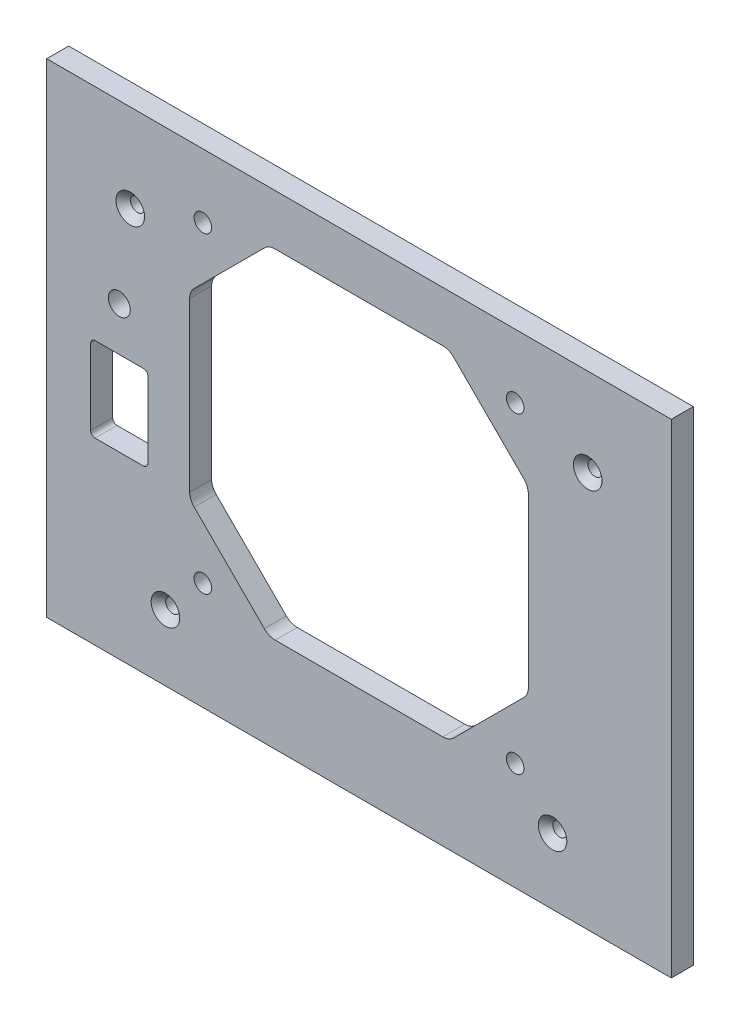
SolidWorks part; units mm, degrees
material "Polycarbonate (PC)"
ref_plane "Front Plane" through (0, 0, 0) normal (0, 0, 1) x (1, 0, 0)
ref_plane "Top Plane" through (0, 0, 0) normal (0, 1, 0) x (1, 0, 0)
ref_plane "Right Plane" through (0, 0, 0) normal (1, 0, 0) x (0, 0, -1)
sketch "Sketch1" plane through (0, 0, 0) normal (0, 0, 1) x (1, 0, 0)
  line L1 (71, -55) -> (-71, -55)
  line L2 (71, -55) -> (71, 55)
  line L3 (71, 55) -> (-71, 55)
  line L4 (-71, -55) -> (-71, 55)
  line L5 (71, -55) -> (-71, 55) construction
  line L6 (71, 55) -> (-71, -55) construction
  point P0 (0, 0)
  dimension "D1" = 142
  dimension "D2" = 110
extrude "Sheet" add sketch "Sketch1" along normal mid plane 5
sketch "Sketch7" plane through (0, 0, 2.5) normal (0, 0, 1) x (1, 0, 0)
  line L0 (-20.5, 43.5) -> (-38.5, 25.5)
  line L1 (20.5, -33.5) -> (-20.5, -33.5)
  line L2 (38.5, -15.5) -> (38.5, 25.5)
  line L3 (20.5, 43.5) -> (-20.5, 43.5)
  line L4 (-38.5, -15.5) -> (-38.5, 25.5)
  line L5 (38.5, -33.5) -> (-38.5, 43.5) construction
  line L6 (38.5, 43.5) -> (-38.5, -33.5) construction
  line L7 (-20.5, -33.5) -> (-38.5, -15.5)
  line L8 (38.5, -15.5) -> (20.5, -33.5)
  line L9 (38.5, 25.5) -> (20.5, 43.5)
  circle A0 centre (0, 5) radius 38.5 construction
  circle A1 centre (-35.5, -30.5) radius 2
  circle A2 centre (35.5, -30.5) radius 2
  circle A3 centre (35.5, 40.5) radius 2
  circle A4 centre (-35.5, 40.5) radius 2
  dimension "D3" = 4
  dimension "D10" = 77
  dimension "D2" = 5
  dimension "D4" = 71
  dimension "D5" = 71
  dimension "D11" = 77
extrude "FanHoles" cut sketch "Sketch7" against normal through all
chamfer "FanChamfer" [suppressed] distance 3 angle 45
fillet "Fillet1" radius 3.5 8 edges at (38.5, 25.5, 0) (38.5, -15.5, 0) (20.5, -33.5, 0) (-38.5, -15.5, 0) (-38.5, 25.5, 0) (-20.5, 43.5, 0) (20.5, 43.5, 0) (-20.5, -33.5, 0)
hole_wizard "Ø3.2 (3.2) TopMountHoles" positions "Sketch9" profile "Sketch10" hole size "Ø3.2" standard "ANSI Metric" end condition through all
sketch "Sketch9" plane through (0, 0, 2.5) normal (0, 0, 1) x (1, 0, 0)
  line L0 (71, 55) -> (-71, 55) construction
  line L1 (-71, 55) -> (-71, -55) construction
  line L2 (71, -55) -> (71, 55) construction
  point P0 (-52, 35)
  point P2 (52, 35)
  dimension "D1" = 20
  dimension "D2" = 19
  dimension "D3" = 19
sketch "Sketch10" plane through (-52, 35, 2.5) normal (1, 0, 0) x (0, -1, 0)
  line L0 (0, 0) -> (0, 5)
  line L1 (0, 5) -> (1.6, 5)
  line L2 (1.6, 5) -> (1.6, 1.65)
  line L3 (1.6, 1.65) -> (3.25, 0)
  line L5 (3.25, 0) -> (0, 0)
  line L6 (-1.6, 1.65) -> (-3.25, 0) construction
  line L11 (0, -6.35) -> (0, 107.95) construction
  dimension "Thru Hole Dia." = 3.2
  dimension "Thru Hole Depth" = 5
  dimension "Near C'Sink Dia." = 6.5
  dimension "Near C'Sink Angle" = 90
hole_wizard "Ø3.2 (3.2) BottomMountHoles" positions "Sketch11" profile "Sketch12" hole size "Ø3.2" standard "ANSI Metric" end condition through all
sketch "Sketch11" plane through (0, 0, 2.5) normal (0, 0, 1) x (1, 0, 0)
  line L0 (-71, -55) -> (71, -55) construction
  line L1 (-71, 55) -> (-71, -55) construction
  line L2 (71, -55) -> (71, 55) construction
  point P0 (-44, -40)
  point P2 (44, -40)
  dimension "D1" = 15
  dimension "D2" = 27
  dimension "D3" = 27
sketch "Sketch12" plane through (-44, -40, 2.5) normal (1, 0, 0) x (0, -1, 0)
  line L0 (0, 0) -> (0, 5)
  line L1 (0, 5) -> (1.6, 5)
  line L2 (1.6, 5) -> (1.6, 1.65)
  line L3 (1.6, 1.65) -> (3.25, 0)
  line L5 (3.25, 0) -> (0, 0)
  line L6 (-1.6, 1.65) -> (-3.25, 0) construction
  line L11 (0, -6.35) -> (0, 107.95) construction
  dimension "Thru Hole Dia." = 3.2
  dimension "Thru Hole Depth" = 5
  dimension "Near C'Sink Dia." = 6.5
  dimension "Near C'Sink Angle" = 90
sketch "Sketch13" plane through (0, 0, 2.5) normal (0, 0, 1) x (1, 0, 0)
  line L0 (-71, 55) -> (-71, -55) construction
  line L1 (-60, 5) -> (-49, 5)
  line L2 (-61, 4) -> (-61, -13.2)
  line L3 (-60, -14.2) -> (-49, -14.2)
  line L4 (-48, 4) -> (-48, -13.2)
  line L5 (71, 55) -> (-71, 55) construction
  arc A0 (-49, -14.2) -> (-48, -13.2) centre (-49, -13.2) ccw
  arc A1 (-61, -13.2) -> (-60, -14.2) centre (-60, -13.2) ccw
  arc A2 (-49, 5) -> (-48, 4) centre (-49, 4) cw
  arc A3 (-60, 5) -> (-61, 4) centre (-60, 4) ccw
  point P8 (-61, -14.2)
  point P11 (-48, 5)
  point P14 (-61, 5)
  dimension "D3" = 1
  dimension "D1" = 13
  dimension "D2" = 19.2
  dimension "D4" = 10
  dimension "D5" = 50
extrude "SwitchSlot" cut sketch "Sketch13" against normal through all
sketch "Sketch8" plane through (0, 0, 2.5) normal (0, 0, 1) x (1, 0, 0)
  line L0 (-49, 5) -> (-60, 5) construction
  line L1 (71, 55) -> (-71, 55) construction
  circle A0 centre (-54.5, 15) radius 2.5
  point P7 (-54.5, 5)
  dimension "D1" = 40
  dimension "D2" = 5
extrude "LEDHole" cut sketch "Sketch8" against normal through all
equation "\"D3@Sketch9\"=\"D2@Sketch9\""
equation "\"D3@Sketch11\"=\"D2@Sketch11\""
